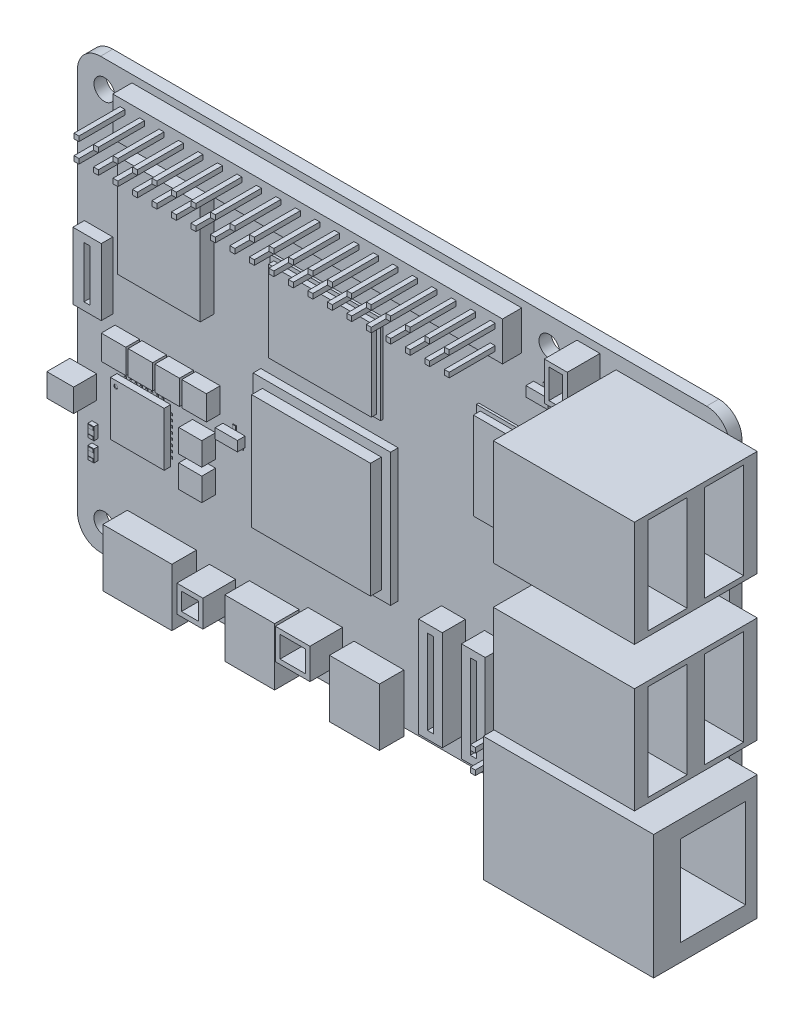
SolidWorks part; units mm, degrees
ref_plane "Front Plane" through (0, 0, 0) normal (0, 0, 1) x (1, 0, 0)
ref_plane "Top Plane" through (0, 0, 0) normal (0, 1, 0) x (1, 0, 0)
ref_plane "Right Plane" through (0, 0, 0) normal (1, 0, 0) x (0, 0, -1)
sketch "Sketch1" plane through (0, 0, 0) normal (0, 0, 1) x (1, 0, 0)
  line L0 (3, 0) -> (82, 0)
  line L1 (85, 3) -> (85, 53)
  line L2 (82, 56) -> (3, 56)
  line L3 (0, 53) -> (0, 3)
  arc A0 (82, 0) -> (85, 3) centre (82, 3) ccw
  arc A1 (85, 53) -> (82, 56) centre (82, 53) ccw
  arc A2 (3, 56) -> (0, 53) centre (3, 53) ccw
  arc A3 (0, 3) -> (3, 0) centre (3, 3) ccw
extrude "PCB" add sketch "Sketch1" along normal blind 1.6
ref_plane "Plane_z1_6" through (0, 0, 1.6) normal (0, 0, 1) x (1, 0, 0)
sketch "Sketch2" plane through (0, 0, 1.6) normal (0, 0, 1) x (1, 0, 0)
  line L1 (7.1, 49.96) -> (57.9, 49.96)
  line L2 (7.1, 49.96) -> (7.1, 55.04)
  line L3 (7.1, 55.04) -> (57.9, 55.04)
  line L4 (57.9, 49.96) -> (57.9, 55.04)
  line L6 (58.76, 6.76) -> (63.84, 6.76)
  line L7 (58.76, 6.76) -> (58.76, 11.84)
  line L8 (58.76, 11.84) -> (63.84, 11.84)
  line L9 (63.84, 6.76) -> (63.84, 11.84)
extrude "Header_Blocks" add sketch "Sketch2" along normal blind 2.5
ref_plane "Plane_z4_1" through (0, 0, 4.1) normal (0, 0, 1) x (1, 0, 0)
sketch "Sketch3" plane through (0, 0, 4.1) normal (0, 0, 1) x (1, 0, 0)
  line L1 (8.05, 50.91) -> (8.69, 50.91)
  line L2 (8.05, 50.91) -> (8.05, 51.55)
  line L3 (8.05, 51.55) -> (8.69, 51.55)
  line L4 (8.69, 50.91) -> (8.69, 51.55)
  line L6 (8.05, 53.45) -> (8.69, 53.45)
  line L7 (8.05, 53.45) -> (8.05, 54.09)
  line L8 (8.05, 54.09) -> (8.69, 54.09)
  line L9 (8.69, 53.45) -> (8.69, 54.09)
  line L11 (10.59, 50.91) -> (11.23, 50.91)
  line L12 (10.59, 50.91) -> (10.59, 51.55)
  line L13 (10.59, 51.55) -> (11.23, 51.55)
  line L14 (11.23, 50.91) -> (11.23, 51.55)
  line L16 (10.59, 53.45) -> (11.23, 53.45)
  line L17 (10.59, 53.45) -> (10.59, 54.09)
  line L18 (10.59, 54.09) -> (11.23, 54.09)
  line L19 (11.23, 53.45) -> (11.23, 54.09)
  line L21 (13.13, 50.91) -> (13.77, 50.91)
  line L22 (13.13, 50.91) -> (13.13, 51.55)
  line L23 (13.13, 51.55) -> (13.77, 51.55)
  line L24 (13.77, 50.91) -> (13.77, 51.55)
  line L26 (13.13, 53.45) -> (13.77, 53.45)
  line L27 (13.13, 53.45) -> (13.13, 54.09)
  line L28 (13.13, 54.09) -> (13.77, 54.09)
  line L29 (13.77, 53.45) -> (13.77, 54.09)
  line L31 (15.67, 50.91) -> (16.31, 50.91)
  line L32 (15.67, 50.91) -> (15.67, 51.55)
  line L33 (15.67, 51.55) -> (16.31, 51.55)
  line L34 (16.31, 50.91) -> (16.31, 51.55)
  line L36 (15.67, 53.45) -> (16.31, 53.45)
  line L37 (15.67, 53.45) -> (15.67, 54.09)
  line L38 (15.67, 54.09) -> (16.31, 54.09)
  line L39 (16.31, 53.45) -> (16.31, 54.09)
  line L41 (18.21, 50.91) -> (18.85, 50.91)
  line L42 (18.21, 50.91) -> (18.21, 51.55)
  line L43 (18.21, 51.55) -> (18.85, 51.55)
  line L44 (18.85, 50.91) -> (18.85, 51.55)
  line L46 (18.21, 53.45) -> (18.85, 53.45)
  line L47 (18.21, 53.45) -> (18.21, 54.09)
  line L48 (18.21, 54.09) -> (18.85, 54.09)
  line L49 (18.85, 53.45) -> (18.85, 54.09)
  line L51 (20.75, 50.91) -> (21.39, 50.91)
  line L52 (20.75, 50.91) -> (20.75, 51.55)
  line L53 (20.75, 51.55) -> (21.39, 51.55)
  line L54 (21.39, 50.91) -> (21.39, 51.55)
  line L56 (20.75, 53.45) -> (21.39, 53.45)
  line L57 (20.75, 53.45) -> (20.75, 54.09)
  line L58 (20.75, 54.09) -> (21.39, 54.09)
  line L59 (21.39, 53.45) -> (21.39, 54.09)
  line L61 (23.29, 50.91) -> (23.93, 50.91)
  line L62 (23.29, 50.91) -> (23.29, 51.55)
  line L63 (23.29, 51.55) -> (23.93, 51.55)
  line L64 (23.93, 50.91) -> (23.93, 51.55)
  line L66 (23.29, 53.45) -> (23.93, 53.45)
  line L67 (23.29, 53.45) -> (23.29, 54.09)
  line L68 (23.29, 54.09) -> (23.93, 54.09)
  line L69 (23.93, 53.45) -> (23.93, 54.09)
  line L71 (25.83, 50.91) -> (26.47, 50.91)
  line L72 (25.83, 50.91) -> (25.83, 51.55)
  line L73 (25.83, 51.55) -> (26.47, 51.55)
  line L74 (26.47, 50.91) -> (26.47, 51.55)
  line L76 (25.83, 53.45) -> (26.47, 53.45)
  line L77 (25.83, 53.45) -> (25.83, 54.09)
  line L78 (25.83, 54.09) -> (26.47, 54.09)
  line L79 (26.47, 53.45) -> (26.47, 54.09)
  line L81 (28.37, 50.91) -> (29.01, 50.91)
  line L82 (28.37, 50.91) -> (28.37, 51.55)
  line L83 (28.37, 51.55) -> (29.01, 51.55)
  line L84 (29.01, 50.91) -> (29.01, 51.55)
  line L86 (28.37, 53.45) -> (29.01, 53.45)
  line L87 (28.37, 53.45) -> (28.37, 54.09)
  line L88 (28.37, 54.09) -> (29.01, 54.09)
  line L89 (29.01, 53.45) -> (29.01, 54.09)
  line L91 (30.91, 50.91) -> (31.55, 50.91)
  line L92 (30.91, 50.91) -> (30.91, 51.55)
  line L93 (30.91, 51.55) -> (31.55, 51.55)
  line L94 (31.55, 50.91) -> (31.55, 51.55)
  line L96 (30.91, 53.45) -> (31.55, 53.45)
  line L97 (30.91, 53.45) -> (30.91, 54.09)
  line L98 (30.91, 54.09) -> (31.55, 54.09)
  line L99 (31.55, 53.45) -> (31.55, 54.09)
  line L101 (33.45, 50.91) -> (34.09, 50.91)
  line L102 (33.45, 50.91) -> (33.45, 51.55)
  line L103 (33.45, 51.55) -> (34.09, 51.55)
  line L104 (34.09, 50.91) -> (34.09, 51.55)
  line L106 (33.45, 53.45) -> (34.09, 53.45)
  line L107 (33.45, 53.45) -> (33.45, 54.09)
  line L108 (33.45, 54.09) -> (34.09, 54.09)
  line L109 (34.09, 53.45) -> (34.09, 54.09)
  line L111 (35.99, 50.91) -> (36.63, 50.91)
  line L112 (35.99, 50.91) -> (35.99, 51.55)
  line L113 (35.99, 51.55) -> (36.63, 51.55)
  line L114 (36.63, 50.91) -> (36.63, 51.55)
  line L116 (35.99, 53.45) -> (36.63, 53.45)
  line L117 (35.99, 53.45) -> (35.99, 54.09)
  line L118 (35.99, 54.09) -> (36.63, 54.09)
  line L119 (36.63, 53.45) -> (36.63, 54.09)
  line L121 (38.53, 50.91) -> (39.17, 50.91)
  line L122 (38.53, 50.91) -> (38.53, 51.55)
  line L123 (38.53, 51.55) -> (39.17, 51.55)
  line L124 (39.17, 50.91) -> (39.17, 51.55)
  line L126 (38.53, 53.45) -> (39.17, 53.45)
  line L127 (38.53, 53.45) -> (38.53, 54.09)
  line L128 (38.53, 54.09) -> (39.17, 54.09)
  line L129 (39.17, 53.45) -> (39.17, 54.09)
  line L131 (41.07, 50.91) -> (41.71, 50.91)
  line L132 (41.07, 50.91) -> (41.07, 51.55)
  line L133 (41.07, 51.55) -> (41.71, 51.55)
  line L134 (41.71, 50.91) -> (41.71, 51.55)
  line L136 (41.07, 53.45) -> (41.71, 53.45)
  line L137 (41.07, 53.45) -> (41.07, 54.09)
  line L138 (41.07, 54.09) -> (41.71, 54.09)
  line L139 (41.71, 53.45) -> (41.71, 54.09)
  line L141 (43.61, 50.91) -> (44.25, 50.91)
  line L142 (43.61, 50.91) -> (43.61, 51.55)
  line L143 (43.61, 51.55) -> (44.25, 51.55)
  line L144 (44.25, 50.91) -> (44.25, 51.55)
  line L146 (43.61, 53.45) -> (44.25, 53.45)
  line L147 (43.61, 53.45) -> (43.61, 54.09)
  line L148 (43.61, 54.09) -> (44.25, 54.09)
  line L149 (44.25, 53.45) -> (44.25, 54.09)
  line L151 (46.15, 50.91) -> (46.79, 50.91)
  line L152 (46.15, 50.91) -> (46.15, 51.55)
  line L153 (46.15, 51.55) -> (46.79, 51.55)
  line L154 (46.79, 50.91) -> (46.79, 51.55)
  line L156 (46.15, 53.45) -> (46.79, 53.45)
  line L157 (46.15, 53.45) -> (46.15, 54.09)
  line L158 (46.15, 54.09) -> (46.79, 54.09)
  line L159 (46.79, 53.45) -> (46.79, 54.09)
  line L161 (48.69, 50.91) -> (49.33, 50.91)
  line L162 (48.69, 50.91) -> (48.69, 51.55)
  line L163 (48.69, 51.55) -> (49.33, 51.55)
  line L164 (49.33, 50.91) -> (49.33, 51.55)
  line L166 (48.69, 53.45) -> (49.33, 53.45)
  line L167 (48.69, 53.45) -> (48.69, 54.09)
  line L168 (48.69, 54.09) -> (49.33, 54.09)
  line L169 (49.33, 53.45) -> (49.33, 54.09)
  line L171 (51.23, 50.91) -> (51.87, 50.91)
  line L172 (51.23, 50.91) -> (51.23, 51.55)
  line L173 (51.23, 51.55) -> (51.87, 51.55)
  line L174 (51.87, 50.91) -> (51.87, 51.55)
  line L176 (51.23, 53.45) -> (51.87, 53.45)
  line L177 (51.23, 53.45) -> (51.23, 54.09)
  line L178 (51.23, 54.09) -> (51.87, 54.09)
  line L179 (51.87, 53.45) -> (51.87, 54.09)
  line L181 (53.77, 50.91) -> (54.41, 50.91)
  line L182 (53.77, 50.91) -> (53.77, 51.55)
  line L183 (53.77, 51.55) -> (54.41, 51.55)
  line L184 (54.41, 50.91) -> (54.41, 51.55)
  line L186 (53.77, 53.45) -> (54.41, 53.45)
  line L187 (53.77, 53.45) -> (53.77, 54.09)
  line L188 (53.77, 54.09) -> (54.41, 54.09)
  line L189 (54.41, 53.45) -> (54.41, 54.09)
  line L191 (56.31, 50.91) -> (56.95, 50.91)
  line L192 (56.31, 50.91) -> (56.31, 51.55)
  line L193 (56.31, 51.55) -> (56.95, 51.55)
  line L194 (56.95, 50.91) -> (56.95, 51.55)
  line L196 (56.31, 53.45) -> (56.95, 53.45)
  line L197 (56.31, 53.45) -> (56.31, 54.09)
  line L198 (56.31, 54.09) -> (56.95, 54.09)
  line L199 (56.95, 53.45) -> (56.95, 54.09)
  line L201 (59.71, 7.71) -> (60.35, 7.71)
  line L202 (59.71, 7.71) -> (59.71, 8.35)
  line L203 (59.71, 8.35) -> (60.35, 8.35)
  line L204 (60.35, 7.71) -> (60.35, 8.35)
  line L206 (59.71, 10.25) -> (60.35, 10.25)
  line L207 (59.71, 10.25) -> (59.71, 10.89)
  line L208 (59.71, 10.89) -> (60.35, 10.89)
  line L209 (60.35, 10.25) -> (60.35, 10.89)
  line L211 (62.25, 7.71) -> (62.89, 7.71)
  line L212 (62.25, 7.71) -> (62.25, 8.35)
  line L213 (62.25, 8.35) -> (62.89, 8.35)
  line L214 (62.89, 7.71) -> (62.89, 8.35)
  line L216 (62.25, 10.25) -> (62.89, 10.25)
  line L217 (62.25, 10.25) -> (62.25, 10.89)
  line L218 (62.25, 10.89) -> (62.89, 10.89)
  line L219 (62.89, 10.25) -> (62.89, 10.89)
extrude "Header_Pins" add sketch "Sketch3" along normal blind 6
sketch "Sketch4" plane through (0, 0, 1.6) normal (0, 0, 1) x (1, 0, 0)
  line L1 (6.125, 14.1) -> (6.375, 14.1)
  line L2 (6.125, 14.1) -> (6.125, 14.4)
  line L3 (6.125, 14.4) -> (6.375, 14.4)
  line L4 (6.375, 14.1) -> (6.375, 14.4)
  line L6 (5, 15.225) -> (5.3, 15.225)
  line L7 (5, 15.225) -> (5, 15.475)
  line L8 (5, 15.475) -> (5.3, 15.475)
  line L9 (5.3, 15.225) -> (5.3, 15.475)
  line L11 (6.125, 21.2) -> (6.375, 21.2)
  line L12 (6.125, 21.2) -> (6.125, 21.5)
  line L13 (6.125, 21.5) -> (6.375, 21.5)
  line L14 (6.375, 21.2) -> (6.375, 21.5)
  line L16 (12.1, 15.225) -> (12.4, 15.225)
  line L17 (12.1, 15.225) -> (12.1, 15.475)
  line L18 (12.1, 15.475) -> (12.4, 15.475)
  line L19 (12.4, 15.225) -> (12.4, 15.475)
  line L21 (6.825, 14.1) -> (7.075, 14.1)
  line L22 (6.825, 14.1) -> (6.825, 14.4)
  line L23 (6.825, 14.4) -> (7.075, 14.4)
  line L24 (7.075, 14.1) -> (7.075, 14.4)
  line L26 (5, 15.925) -> (5.3, 15.925)
  line L27 (5, 15.925) -> (5, 16.175)
  line L28 (5, 16.175) -> (5.3, 16.175)
  line L29 (5.3, 15.925) -> (5.3, 16.175)
  line L31 (6.825, 21.2) -> (7.075, 21.2)
  line L32 (6.825, 21.2) -> (6.825, 21.5)
  line L33 (6.825, 21.5) -> (7.075, 21.5)
  line L34 (7.075, 21.2) -> (7.075, 21.5)
  line L36 (12.1, 15.925) -> (12.4, 15.925)
  line L37 (12.1, 15.925) -> (12.1, 16.175)
  line L38 (12.1, 16.175) -> (12.4, 16.175)
  line L39 (12.4, 15.925) -> (12.4, 16.175)
  line L41 (7.525, 14.1) -> (7.775, 14.1)
  line L42 (7.525, 14.1) -> (7.525, 14.4)
  line L43 (7.525, 14.4) -> (7.775, 14.4)
  line L44 (7.775, 14.1) -> (7.775, 14.4)
  line L46 (5, 16.625) -> (5.3, 16.625)
  line L47 (5, 16.625) -> (5, 16.875)
  line L48 (5, 16.875) -> (5.3, 16.875)
  line L49 (5.3, 16.625) -> (5.3, 16.875)
  line L51 (7.525, 21.2) -> (7.775, 21.2)
  line L52 (7.525, 21.2) -> (7.525, 21.5)
  line L53 (7.525, 21.5) -> (7.775, 21.5)
  line L54 (7.775, 21.2) -> (7.775, 21.5)
  line L56 (12.1, 16.625) -> (12.4, 16.625)
  line L57 (12.1, 16.625) -> (12.1, 16.875)
  line L58 (12.1, 16.875) -> (12.4, 16.875)
  line L59 (12.4, 16.625) -> (12.4, 16.875)
  line L61 (8.225, 14.1) -> (8.475, 14.1)
  line L62 (8.225, 14.1) -> (8.225, 14.4)
  line L63 (8.225, 14.4) -> (8.475, 14.4)
  line L64 (8.475, 14.1) -> (8.475, 14.4)
  line L66 (5, 17.325) -> (5.3, 17.325)
  line L67 (5, 17.325) -> (5, 17.575)
  line L68 (5, 17.575) -> (5.3, 17.575)
  line L69 (5.3, 17.325) -> (5.3, 17.575)
  line L71 (8.225, 21.2) -> (8.475, 21.2)
  line L72 (8.225, 21.2) -> (8.225, 21.5)
  line L73 (8.225, 21.5) -> (8.475, 21.5)
  line L74 (8.475, 21.2) -> (8.475, 21.5)
  line L76 (12.1, 17.325) -> (12.4, 17.325)
  line L77 (12.1, 17.325) -> (12.1, 17.575)
  line L78 (12.1, 17.575) -> (12.4, 17.575)
  line L79 (12.4, 17.325) -> (12.4, 17.575)
  line L81 (8.925, 14.1) -> (9.175, 14.1)
  line L82 (8.925, 14.1) -> (8.925, 14.4)
  line L83 (8.925, 14.4) -> (9.175, 14.4)
  line L84 (9.175, 14.1) -> (9.175, 14.4)
  line L86 (5, 18.025) -> (5.3, 18.025)
  line L87 (5, 18.025) -> (5, 18.275)
  line L88 (5, 18.275) -> (5.3, 18.275)
  line L89 (5.3, 18.025) -> (5.3, 18.275)
  line L91 (8.925, 21.2) -> (9.175, 21.2)
  line L92 (8.925, 21.2) -> (8.925, 21.5)
  line L93 (8.925, 21.5) -> (9.175, 21.5)
  line L94 (9.175, 21.2) -> (9.175, 21.5)
  line L96 (12.1, 18.025) -> (12.4, 18.025)
  line L97 (12.1, 18.025) -> (12.1, 18.275)
  line L98 (12.1, 18.275) -> (12.4, 18.275)
  line L99 (12.4, 18.025) -> (12.4, 18.275)
  line L101 (9.625, 14.1) -> (9.875, 14.1)
  line L102 (9.625, 14.1) -> (9.625, 14.4)
  line L103 (9.625, 14.4) -> (9.875, 14.4)
  line L104 (9.875, 14.1) -> (9.875, 14.4)
  line L106 (5, 18.725) -> (5.3, 18.725)
  line L107 (5, 18.725) -> (5, 18.975)
  line L108 (5, 18.975) -> (5.3, 18.975)
  line L109 (5.3, 18.725) -> (5.3, 18.975)
  line L111 (9.625, 21.2) -> (9.875, 21.2)
  line L112 (9.625, 21.2) -> (9.625, 21.5)
  line L113 (9.625, 21.5) -> (9.875, 21.5)
  line L114 (9.875, 21.2) -> (9.875, 21.5)
  line L116 (12.1, 18.725) -> (12.4, 18.725)
  line L117 (12.1, 18.725) -> (12.1, 18.975)
  line L118 (12.1, 18.975) -> (12.4, 18.975)
  line L119 (12.4, 18.725) -> (12.4, 18.975)
  line L121 (10.325, 14.1) -> (10.575, 14.1)
  line L122 (10.325, 14.1) -> (10.325, 14.4)
  line L123 (10.325, 14.4) -> (10.575, 14.4)
  line L124 (10.575, 14.1) -> (10.575, 14.4)
  line L126 (5, 19.425) -> (5.3, 19.425)
  line L127 (5, 19.425) -> (5, 19.675)
  line L128 (5, 19.675) -> (5.3, 19.675)
  line L129 (5.3, 19.425) -> (5.3, 19.675)
  line L131 (10.325, 21.2) -> (10.575, 21.2)
  line L132 (10.325, 21.2) -> (10.325, 21.5)
  line L133 (10.325, 21.5) -> (10.575, 21.5)
  line L134 (10.575, 21.2) -> (10.575, 21.5)
  line L136 (12.1, 19.425) -> (12.4, 19.425)
  line L137 (12.1, 19.425) -> (12.1, 19.675)
  line L138 (12.1, 19.675) -> (12.4, 19.675)
  line L139 (12.4, 19.425) -> (12.4, 19.675)
  line L141 (11.025, 14.1) -> (11.275, 14.1)
  line L142 (11.025, 14.1) -> (11.025, 14.4)
  line L143 (11.025, 14.4) -> (11.275, 14.4)
  line L144 (11.275, 14.1) -> (11.275, 14.4)
  line L146 (5, 20.125) -> (5.3, 20.125)
  line L147 (5, 20.125) -> (5, 20.375)
  line L148 (5, 20.375) -> (5.3, 20.375)
  line L149 (5.3, 20.125) -> (5.3, 20.375)
  line L151 (11.025, 21.2) -> (11.275, 21.2)
  line L152 (11.025, 21.2) -> (11.025, 21.5)
  line L153 (11.025, 21.5) -> (11.275, 21.5)
  line L154 (11.275, 21.2) -> (11.275, 21.5)
  line L156 (12.1, 20.125) -> (12.4, 20.125)
  line L157 (12.1, 20.125) -> (12.1, 20.375)
  line L158 (12.1, 20.375) -> (12.4, 20.375)
  line L159 (12.4, 20.125) -> (12.4, 20.375)
  line L161 (66.275, 43.15) -> (66.525, 43.15)
  line L162 (66.275, 43.15) -> (66.275, 43.45)
  line L163 (66.275, 43.45) -> (66.525, 43.45)
  line L164 (66.525, 43.15) -> (66.525, 43.45)
  line L166 (65.2, 44.475) -> (65.5, 44.475)
  line L167 (65.2, 44.475) -> (65.2, 44.725)
  line L168 (65.2, 44.725) -> (65.5, 44.725)
  line L169 (65.5, 44.475) -> (65.5, 44.725)
  line L171 (66.275, 47.75) -> (66.525, 47.75)
  line L172 (66.275, 47.75) -> (66.275, 48.05)
  line L173 (66.275, 48.05) -> (66.525, 48.05)
  line L174 (66.525, 47.75) -> (66.525, 48.05)
  line L176 (69.3, 44.475) -> (69.6, 44.475)
  line L177 (69.3, 44.475) -> (69.3, 44.725)
  line L178 (69.3, 44.725) -> (69.6, 44.725)
  line L179 (69.6, 44.475) -> (69.6, 44.725)
  line L181 (66.9417, 43.15) -> (67.1917, 43.15)
  line L182 (66.9417, 43.15) -> (66.9417, 43.45)
  line L183 (66.9417, 43.45) -> (67.1917, 43.45)
  line L184 (67.1917, 43.15) -> (67.1917, 43.45)
  line L186 (65.2, 45.1417) -> (65.5, 45.1417)
  line L187 (65.2, 45.1417) -> (65.2, 45.3917)
  line L188 (65.2, 45.3917) -> (65.5, 45.3917)
  line L189 (65.5, 45.1417) -> (65.5, 45.3917)
  line L191 (66.9417, 47.75) -> (67.1917, 47.75)
  line L192 (66.9417, 47.75) -> (66.9417, 48.05)
  line L193 (66.9417, 48.05) -> (67.1917, 48.05)
  line L194 (67.1917, 47.75) -> (67.1917, 48.05)
  line L196 (69.3, 45.1417) -> (69.6, 45.1417)
  line L197 (69.3, 45.1417) -> (69.3, 45.3917)
  line L198 (69.3, 45.3917) -> (69.6, 45.3917)
  line L199 (69.6, 45.1417) -> (69.6, 45.3917)
  line L201 (67.6083, 43.15) -> (67.8583, 43.15)
  line L202 (67.6083, 43.15) -> (67.6083, 43.45)
  line L203 (67.6083, 43.45) -> (67.8583, 43.45)
  line L204 (67.8583, 43.15) -> (67.8583, 43.45)
  line L206 (65.2, 45.8083) -> (65.5, 45.8083)
  line L207 (65.2, 45.8083) -> (65.2, 46.0583)
  line L208 (65.2, 46.0583) -> (65.5, 46.0583)
  line L209 (65.5, 45.8083) -> (65.5, 46.0583)
  line L211 (67.6083, 47.75) -> (67.8583, 47.75)
  line L212 (67.6083, 47.75) -> (67.6083, 48.05)
  line L213 (67.6083, 48.05) -> (67.8583, 48.05)
  line L214 (67.8583, 47.75) -> (67.8583, 48.05)
  line L216 (69.3, 45.8083) -> (69.6, 45.8083)
  line L217 (69.3, 45.8083) -> (69.3, 46.0583)
  line L218 (69.3, 46.0583) -> (69.6, 46.0583)
  line L219 (69.6, 45.8083) -> (69.6, 46.0583)
  line L221 (68.275, 43.15) -> (68.525, 43.15)
  line L222 (68.275, 43.15) -> (68.275, 43.45)
  line L223 (68.275, 43.45) -> (68.525, 43.45)
  line L224 (68.525, 43.15) -> (68.525, 43.45)
  line L226 (65.2, 46.475) -> (65.5, 46.475)
  line L227 (65.2, 46.475) -> (65.2, 46.725)
  line L228 (65.2, 46.725) -> (65.5, 46.725)
  line L229 (65.5, 46.475) -> (65.5, 46.725)
  line L231 (68.275, 47.75) -> (68.525, 47.75)
  line L232 (68.275, 47.75) -> (68.275, 48.05)
  line L233 (68.275, 48.05) -> (68.525, 48.05)
  line L234 (68.525, 47.75) -> (68.525, 48.05)
  line L236 (69.3, 46.475) -> (69.6, 46.475)
  line L237 (69.3, 46.475) -> (69.3, 46.725)
  line L238 (69.3, 46.725) -> (69.6, 46.725)
  line L239 (69.6, 46.475) -> (69.6, 46.725)
extrude "Parts_add00" add sketch "Sketch4" along normal blind 0.05
sketch "Sketch5" plane through (0, 0, 1.6) normal (0, 0, 1) x (1, 0, 0)
  line L1 (19.35, 20.85) -> (19.75, 20.85)
  line L2 (19.35, 20.85) -> (19.35, 21.55)
  line L3 (19.35, 21.55) -> (19.75, 21.55)
  line L4 (19.75, 20.85) -> (19.75, 21.55)
  line L6 (21.25, 20.85) -> (21.65, 20.85)
  line L7 (21.25, 20.85) -> (21.25, 21.55)
  line L8 (21.25, 21.55) -> (21.65, 21.55)
  line L9 (21.65, 20.85) -> (21.65, 21.55)
  line L11 (20.3, 22.45) -> (20.7, 22.45)
  line L12 (20.3, 22.45) -> (20.3, 23.15)
  line L13 (20.3, 23.15) -> (20.7, 23.15)
  line L14 (20.7, 22.45) -> (20.7, 23.15)
  line L16 (58.35, 16.85) -> (58.75, 16.85)
  line L17 (58.35, 16.85) -> (58.35, 17.55)
  line L18 (58.35, 17.55) -> (58.75, 17.55)
  line L19 (58.75, 16.85) -> (58.75, 17.55)
  line L21 (60.25, 16.85) -> (60.65, 16.85)
  line L22 (60.25, 16.85) -> (60.25, 17.55)
  line L23 (60.25, 17.55) -> (60.65, 17.55)
  line L24 (60.65, 16.85) -> (60.65, 17.55)
  line L26 (59.3, 18.45) -> (59.7, 18.45)
  line L27 (59.3, 18.45) -> (59.3, 19.15)
  line L28 (59.3, 19.15) -> (59.7, 19.15)
  line L29 (59.7, 18.45) -> (59.7, 19.15)
  line L31 (59.85, 45.85) -> (60.25, 45.85)
  line L32 (59.85, 45.85) -> (59.85, 46.55)
  line L33 (59.85, 46.55) -> (60.25, 46.55)
  line L34 (60.25, 45.85) -> (60.25, 46.55)
  line L36 (61.75, 45.85) -> (62.15, 45.85)
  line L37 (61.75, 45.85) -> (61.75, 46.55)
  line L38 (61.75, 46.55) -> (62.15, 46.55)
  line L39 (62.15, 45.85) -> (62.15, 46.55)
  line L41 (60.8, 47.45) -> (61.2, 47.45)
  line L42 (60.8, 47.45) -> (60.8, 48.15)
  line L43 (60.8, 48.15) -> (61.2, 48.15)
  line L44 (61.2, 47.45) -> (61.2, 48.15)
extrude "Parts_add01" add sketch "Sketch5" along normal blind 0.1
sketch "Sketch6" plane through (0, 0, 1.6) normal (0, 0, 1) x (1, 0, 0)
  line L1 (25.4, 33.4) -> (39.8, 33.4)
  line L2 (25.4, 33.4) -> (25.4, 45)
  line L3 (25.4, 45) -> (39.8, 45)
  line L4 (39.8, 33.4) -> (39.8, 45)
  line L6 (52.3, 29.1) -> (65.2, 29.1)
  line L7 (52.3, 29.1) -> (52.3, 41.5)
  line L8 (52.3, 41.5) -> (65.2, 41.5)
  line L9 (65.2, 29.1) -> (65.2, 41.5)
extrude "Parts_add02" add sketch "Sketch6" along normal blind 0.3
sketch "Sketch7" plane through (0, 0, 1.6) normal (0, 0, 1) x (1, 0, 0)
  line L1 (1.9, 10.2) -> (2.7, 10.2)
  line L2 (1.9, 10.2) -> (1.9, 11.8)
  line L3 (1.9, 11.8) -> (2.7, 11.8)
  line L4 (2.7, 10.2) -> (2.7, 11.8)
  line L6 (1.9, 12.7) -> (2.7, 12.7)
  line L7 (1.9, 12.7) -> (1.9, 14.3)
  line L8 (1.9, 14.3) -> (2.7, 14.3)
  line L9 (2.7, 12.7) -> (2.7, 14.3)
extrude "Parts_add03" add sketch "Sketch7" along normal blind 0.55
sketch "Sketch8" plane through (0, 0, 1.6) normal (0, 0, 1) x (1, 0, 0)
  line L0 (62.7, 19.918) -> (65.882, 23.1)
  line L1 (65.882, 23.1) -> (62.7, 26.282)
  line L2 (62.7, 26.282) -> (59.518, 23.1)
  line L3 (59.518, 23.1) -> (62.7, 19.918)
extrude "Parts_add04" add sketch "Sketch8" along normal blind 0.9
sketch "Sketch9" plane through (0, 0, 1.6) normal (0, 0, 1) x (1, 0, 0)
  line L1 (23.9, 13.9) -> (41.8, 13.9)
  line L2 (23.9, 13.9) -> (23.9, 31.2)
  line L3 (23.9, 31.2) -> (41.8, 31.2)
  line L4 (41.8, 13.9) -> (41.8, 31.2)
extrude "Parts_add05" add sketch "Sketch9" along normal blind 1
sketch "Sketch10" plane through (0, 0, 1.6) normal (0, 0, 1) x (1, 0, 0)
  line L1 (0.9, 27.7) -> (4.6, 27.7)
  line L2 (0.9, 27.7) -> (0.9, 36.4)
  line L3 (0.9, 36.4) -> (4.6, 36.4)
  line L4 (4.6, 27.7) -> (4.6, 36.4)
extrude "Parts_add06" add sketch "Sketch10" along normal blind 1.5
sketch "Sketch11" plane through (0, 0, 1.6) normal (0, 0, 1) x (1, 0, 0)
  line L1 (7, 34.3) -> (17.8, 34.3)
  line L2 (7, 34.3) -> (7, 47.6)
  line L3 (7, 47.6) -> (17.8, 47.6)
  line L4 (17.8, 34.3) -> (17.8, 47.6)
  line L6 (4.9, 23.4) -> (8.1, 23.4)
  line L7 (4.9, 23.4) -> (4.9, 26.6)
  line L8 (4.9, 26.6) -> (8.1, 26.6)
  line L9 (8.1, 23.4) -> (8.1, 26.6)
  line L11 (8.4, 23.4) -> (11.6, 23.4)
  line L12 (8.4, 23.4) -> (8.4, 26.6)
  line L13 (8.4, 26.6) -> (11.6, 26.6)
  line L14 (11.6, 23.4) -> (11.6, 26.6)
  line L16 (11.9, 23.4) -> (15.1, 23.4)
  line L17 (11.9, 23.4) -> (11.9, 26.6)
  line L18 (11.9, 26.6) -> (15.1, 26.6)
  line L19 (15.1, 23.4) -> (15.1, 26.6)
  line L21 (15.4, 23.4) -> (18.6, 23.4)
  line L22 (15.4, 23.4) -> (15.4, 26.6)
  line L23 (15.4, 26.6) -> (18.6, 26.6)
  line L24 (18.6, 23.4) -> (18.6, 26.6)
  line L26 (15, 18) -> (18, 18)
  line L27 (15, 18) -> (15, 21)
  line L28 (15, 21) -> (18, 21)
  line L29 (18, 18) -> (18, 21)
  line L31 (15, 14) -> (18, 14)
  line L32 (15, 14) -> (15, 17)
  line L33 (15, 17) -> (18, 17)
  line L34 (18, 14) -> (18, 17)
extrude "Parts_add07" add sketch "Sketch11" along normal blind 1.8
sketch "Sketch12" plane through (0, 0, 1.6) normal (0, 0, 1) x (1, 0, 0)
  line L1 (53.05, 3.2) -> (56.15, 3.2)
  line L2 (53.05, 3.2) -> (53.05, 16.2)
  line L3 (53.05, 16.2) -> (56.15, 16.2)
  line L4 (56.15, 3.2) -> (56.15, 16.2)
  line L6 (47.45, 3.2) -> (50.55, 3.2)
  line L7 (47.45, 3.2) -> (47.45, 16.2)
  line L8 (47.45, 16.2) -> (50.55, 16.2)
  line L9 (50.55, 3.2) -> (50.55, 16.2)
  line L11 (-1, 16.9) -> (2.5, 16.9)
  line L12 (-1, 16.9) -> (-1, 19.9)
  line L13 (-1, 19.9) -> (2.5, 19.9)
  line L14 (2.5, 16.9) -> (2.5, 19.9)
extrude "Parts_add08" add sketch "Sketch12" along normal blind 3
sketch "Sketch13" plane through (0, 0, 1.6) normal (0, 0, 1) x (1, 0, 0)
  line L1 (22.4, -1) -> (28.9, -1)
  line L2 (22.4, -1) -> (22.4, 6.5)
  line L3 (22.4, 6.5) -> (28.9, 6.5)
  line L4 (28.9, -1) -> (28.9, 6.5)
  line L6 (36.05, -1) -> (42.55, -1)
  line L7 (36.05, -1) -> (36.05, 6.5)
  line L8 (36.05, 6.5) -> (42.55, 6.5)
  line L9 (42.55, -1) -> (42.55, 6.5)
  line L11 (6.5, -1) -> (15.5, -1)
  line L12 (6.5, -1) -> (6.5, 6.5)
  line L13 (6.5, 6.5) -> (15.5, 6.5)
  line L14 (15.5, -1) -> (15.5, 6.5)
extrude "Parts_add09" add sketch "Sketch13" along normal blind 3.2
sketch "Sketch14" plane through (0, 0, 1.6) normal (0, 0, 1) x (1, 0, 0)
  line L1 (65.1, 50) -> (68.1, 50)
  line L2 (65.1, 50) -> (65.1, 55)
  line L3 (65.1, 55) -> (68.1, 55)
  line L4 (68.1, 50) -> (68.1, 55)
  line L6 (30.05, 3.3) -> (34.55, 3.3)
  line L7 (30.05, 3.3) -> (30.05, 7.3)
  line L8 (30.05, 7.3) -> (34.55, 7.3)
  line L9 (34.55, 3.3) -> (34.55, 7.3)
  line L11 (17.2, 2.25) -> (20.6, 2.25)
  line L12 (17.2, 2.25) -> (17.2, 5.75)
  line L13 (17.2, 5.75) -> (20.6, 5.75)
  line L14 (20.6, 2.25) -> (20.6, 5.75)
extrude "Parts_add10" add sketch "Sketch14" along normal blind 4.25
sketch "Sketch15" plane through (0, 0, 1.6) normal (0, 0, 1) x (1, 0, 0)
  line L1 (66.4, 1.5) -> (88.6, 1.5)
  line L2 (66.4, 1.5) -> (66.4, 17.7)
  line L3 (66.4, 17.7) -> (88.6, 17.7)
  line L4 (88.6, 1.5) -> (88.6, 17.7)
extrude "Parts_add11" add sketch "Sketch15" along normal blind 13.5
sketch "Sketch16" plane through (0, 0, 1.6) normal (0, 0, 1) x (1, 0, 0)
  line L1 (70.2, 40.4) -> (88.6, 40.4)
  line L2 (70.2, 40.4) -> (70.2, 54.2)
  line L3 (70.2, 54.2) -> (88.6, 54.2)
  line L4 (88.6, 40.4) -> (88.6, 54.2)
  line L6 (70.2, 21.6) -> (88.6, 21.6)
  line L7 (70.2, 21.6) -> (70.2, 35.4)
  line L8 (70.2, 35.4) -> (88.6, 35.4)
  line L9 (88.6, 21.6) -> (88.6, 35.4)
extrude "Parts_add12" add sketch "Sketch16" along normal blind 16
ref_plane "Plane_z1_65" through (0, 0, 1.65) normal (0, 0, 1) x (1, 0, 0)
sketch "Sketch17" plane through (0, 0, 1.65) normal (0, 0, 1) x (1, 0, 0)
  line L1 (5.2, 14.3) -> (12.2, 14.3)
  line L2 (5.2, 14.3) -> (5.2, 21.3)
  line L3 (5.2, 21.3) -> (12.2, 21.3)
  line L4 (12.2, 14.3) -> (12.2, 21.3)
extrude "Parts_add13" add sketch "Sketch17" along normal blind 0.85
sketch "Sketch18" plane through (0, 0, 1.65) normal (0, 0, 1) x (1, 0, 0)
  line L1 (65.4, 43.35) -> (69.4, 43.35)
  line L2 (65.4, 43.35) -> (65.4, 47.85)
  line L3 (65.4, 47.85) -> (69.4, 47.85)
  line L4 (69.4, 43.35) -> (69.4, 47.85)
extrude "Parts_add14" add sketch "Sketch18" along normal blind 0.95
ref_plane "Plane_z1_7" through (0, 0, 1.7) normal (0, 0, 1) x (1, 0, 0)
sketch "Sketch19" plane through (0, 0, 1.7) normal (0, 0, 1) x (1, 0, 0)
  line L1 (19.05, 21.35) -> (21.95, 21.35)
  line L2 (19.05, 21.35) -> (19.05, 22.65)
  line L3 (19.05, 22.65) -> (21.95, 22.65)
  line L4 (21.95, 21.35) -> (21.95, 22.65)
  line L6 (58.05, 17.35) -> (60.95, 17.35)
  line L7 (58.05, 17.35) -> (58.05, 18.65)
  line L8 (58.05, 18.65) -> (60.95, 18.65)
  line L9 (60.95, 17.35) -> (60.95, 18.65)
  line L11 (59.55, 46.35) -> (62.45, 46.35)
  line L12 (59.55, 46.35) -> (59.55, 47.65)
  line L13 (59.55, 47.65) -> (62.45, 47.65)
  line L14 (62.45, 46.35) -> (62.45, 47.65)
extrude "Parts_add15" add sketch "Sketch19" along normal blind 1
ref_plane "Plane_z1_9" through (0, 0, 1.9) normal (0, 0, 1) x (1, 0, 0)
sketch "Sketch20" plane through (0, 0, 1.9) normal (0, 0, 1) x (1, 0, 0)
  line L1 (25.9, 33.9) -> (39.3, 33.9)
  line L2 (25.9, 33.9) -> (25.9, 44.5)
  line L3 (25.9, 44.5) -> (39.3, 44.5)
  line L4 (39.3, 33.9) -> (39.3, 44.5)
extrude "Parts_add16" add sketch "Sketch20" along normal blind 0.7
sketch "Sketch21" plane through (0, 0, 1.9) normal (0, 0, 1) x (1, 0, 0)
  line L1 (52.8, 29.6) -> (64.7, 29.6)
  line L2 (52.8, 29.6) -> (52.8, 41)
  line L3 (52.8, 41) -> (64.7, 41)
  line L4 (64.7, 29.6) -> (64.7, 41)
extrude "Parts_add17" add sketch "Sketch21" along normal blind 0.9
ref_plane "Plane_z2_15" through (0, 0, 2.15) normal (0, 0, 1) x (1, 0, 0)
sketch "Sketch22" plane through (0, 0, 2.15) normal (0, 0, 1) x (1, 0, 0)
  line L1 (1.95, 10.25) -> (2.65, 10.25)
  line L2 (1.95, 10.25) -> (1.95, 10.65)
  line L3 (1.95, 10.65) -> (2.65, 10.65)
  line L4 (2.65, 10.25) -> (2.65, 10.65)
  line L6 (1.95, 11.35) -> (2.65, 11.35)
  line L7 (1.95, 11.35) -> (1.95, 11.75)
  line L8 (1.95, 11.75) -> (2.65, 11.75)
  line L9 (2.65, 11.35) -> (2.65, 11.75)
  line L11 (1.95, 12.75) -> (2.65, 12.75)
  line L12 (1.95, 12.75) -> (1.95, 13.15)
  line L13 (1.95, 13.15) -> (2.65, 13.15)
  line L14 (2.65, 12.75) -> (2.65, 13.15)
  line L16 (1.95, 13.85) -> (2.65, 13.85)
  line L17 (1.95, 13.85) -> (1.95, 14.25)
  line L18 (1.95, 14.25) -> (2.65, 14.25)
  line L19 (2.65, 13.85) -> (2.65, 14.25)
extrude "Parts_add18" add sketch "Sketch22" along normal blind 0.05
ref_plane "Plane_z2_6" through (0, 0, 2.6) normal (0, 0, 1) x (1, 0, 0)
sketch "Sketch23" plane through (0, 0, 2.6) normal (0, 0, 1) x (1, 0, 0)
  line L1 (25.1, 15.05) -> (40.6, 15.05)
  line L2 (25.1, 15.05) -> (25.1, 30.05)
  line L3 (25.1, 30.05) -> (40.6, 30.05)
  line L4 (40.6, 15.05) -> (40.6, 30.05)
extrude "Parts_add19" add sketch "Sketch23" along normal blind 1.4
ref_plane "Plane_x88_6" through (88.6, 0, 0) normal (1, 0, 0) x (0, 0, -1)
sketch "Sketch24" plane through (88.6, 0, 0) normal (1, 0, 0) x (0, 0, -1)
  line L1 (-3.37, 41.05) -> (-8.47, 41.05)
  line L2 (-3.37, 41.05) -> (-3.37, 53.55)
  line L3 (-3.37, 53.55) -> (-8.47, 53.55)
  line L4 (-8.47, 41.05) -> (-8.47, 53.55)
  line L6 (-10.73, 41.05) -> (-15.83, 41.05)
  line L7 (-10.73, 41.05) -> (-10.73, 53.55)
  line L8 (-10.73, 53.55) -> (-15.83, 53.55)
  line L9 (-15.83, 41.05) -> (-15.83, 53.55)
  line L11 (-3.37, 22.25) -> (-8.47, 22.25)
  line L12 (-3.37, 22.25) -> (-3.37, 34.75)
  line L13 (-3.37, 34.75) -> (-8.47, 34.75)
  line L14 (-8.47, 22.25) -> (-8.47, 34.75)
  line L16 (-10.73, 22.25) -> (-15.83, 22.25)
  line L17 (-10.73, 22.25) -> (-10.73, 34.75)
  line L18 (-10.73, 34.75) -> (-15.83, 34.75)
  line L19 (-15.83, 22.25) -> (-15.83, 34.75)
extrude "Parts_cut00" cut sketch "Sketch24" against normal blind 14
sketch "Sketch25" plane through (88.6, 0, 0) normal (1, 0, 0) x (0, 0, -1)
  line L1 (-3.1, 3.75) -> (-11.6, 3.75)
  line L2 (-3.1, 3.75) -> (-3.1, 15.45)
  line L3 (-3.1, 15.45) -> (-11.6, 15.45)
  line L4 (-11.6, 3.75) -> (-11.6, 15.45)
extrude "Parts_cut01" cut sketch "Sketch25" against normal blind 18
ref_plane "Plane_y6" through (0, 6, 0) normal (0, 1, 0) x (1, 0, 0)
sketch "Sketch26" plane through (0, 6, 0) normal (0, 1, 0) x (1, 0, 0)
  line L0 (8.1, -3.2) -> (13.9, -3.2) construction
  line L1 (22.9, -2.2) -> (28.4, -2.2)
  line L2 (22.9, -2.2) -> (22.9, -4.2)
  line L3 (22.9, -4.2) -> (28.4, -4.2)
  line L4 (28.4, -2.2) -> (28.4, -4.2)
  line L5 (8.1, -1.95) -> (13.9, -1.95)
  line L6 (36.55, -2.2) -> (42.05, -2.2)
  line L7 (36.55, -2.2) -> (36.55, -4.2)
  line L8 (36.55, -4.2) -> (42.05, -4.2)
  line L9 (42.05, -2.2) -> (42.05, -4.2)
  line L10 (8.1, -4.45) -> (13.9, -4.45)
  arc A0 (8.1, -1.95) -> (8.1, -4.45) centre (8.1, -3.2) ccw
  arc A1 (13.9, -4.45) -> (13.9, -1.95) centre (13.9, -3.2) ccw
  point P4 (11, -3.2)
extrude "Parts_cut02" cut sketch "Sketch26" against normal blind 7
ref_plane "Plane_z2_5" through (0, 0, 2.5) normal (0, 0, 1) x (1, 0, 0)
sketch "Sketch27" plane through (0, 0, 2.5) normal (0, 0, 1) x (1, 0, 0)
  circle A0 centre (5.9, 20.6) radius 0.25
extrude "Parts_cut03" cut sketch "Sketch27" against normal blind 0.1
sketch "Sketch28" plane through (0, 0, 2.6) normal (0, 0, 1) x (1, 0, 0)
  circle A0 centre (66.1, 47.15) radius 0.25
extrude "Parts_cut04" cut sketch "Sketch28" against normal blind 0.1
ref_plane "Plane_z3_1" through (0, 0, 3.1) normal (0, 0, 1) x (1, 0, 0)
sketch "Sketch29" plane through (0, 0, 3.1) normal (0, 0, 1) x (1, 0, 0)
  line L1 (2.35, 28.7) -> (3.15, 28.7)
  line L2 (2.35, 28.7) -> (2.35, 35.4)
  line L3 (2.35, 35.4) -> (3.15, 35.4)
  line L4 (3.15, 28.7) -> (3.15, 35.4)
extrude "Parts_cut05" cut sketch "Sketch29" against normal blind 1
ref_plane "Plane_z4_6" through (0, 0, 4.6) normal (0, 0, 1) x (1, 0, 0)
sketch "Sketch30" plane through (0, 0, 4.6) normal (0, 0, 1) x (1, 0, 0)
  line L1 (54.2, 4.2) -> (55, 4.2)
  line L2 (54.2, 4.2) -> (54.2, 15.2)
  line L3 (54.2, 15.2) -> (55, 15.2)
  line L4 (55, 4.2) -> (55, 15.2)
  line L6 (48.6, 4.2) -> (49.4, 4.2)
  line L7 (48.6, 4.2) -> (48.6, 15.2)
  line L8 (48.6, 15.2) -> (49.4, 15.2)
  line L9 (49.4, 4.2) -> (49.4, 15.2)
extrude "Parts_cut06" cut sketch "Sketch30" against normal blind 2.5
ref_plane "Plane_z5_85" through (0, 0, 5.85) normal (0, 0, 1) x (1, 0, 0)
sketch "Sketch31" plane through (0, 0, 5.85) normal (0, 0, 1) x (1, 0, 0)
  line L1 (65.7, 50.6) -> (67.5, 50.6)
  line L2 (65.7, 50.6) -> (65.7, 54.4)
  line L3 (65.7, 54.4) -> (67.5, 54.4)
  line L4 (67.5, 50.6) -> (67.5, 54.4)
  line L6 (30.65, 3.9) -> (33.95, 3.9)
  line L7 (30.65, 3.9) -> (30.65, 6.7)
  line L8 (30.65, 6.7) -> (33.95, 6.7)
  line L9 (33.95, 3.9) -> (33.95, 6.7)
  line L11 (17.8, 2.85) -> (20, 2.85)
  line L12 (17.8, 2.85) -> (17.8, 5.15)
  line L13 (17.8, 5.15) -> (20, 5.15)
  line L14 (20, 2.85) -> (20, 5.15)
extrude "Parts_cut07" cut sketch "Sketch31" against normal blind 3.25
sketch "Sketch32" plane through (0, 0, 0) normal (0, 0, 1) x (1, 0, 0)
  circle A0 centre (3.5, 3.5) radius 1.35
  circle A1 centre (3.5, 52.5) radius 1.35
  circle A2 centre (61.5, 3.5) radius 1.35
  circle A3 centre (61.5, 52.5) radius 1.35
extrude "Mount_Holes" cut sketch "Sketch32" against normal through all and the other way through all
equation "\"pcb_l\"= 85mm"
equation "\"pcb_w\"= 56mm"
equation "\"pcb_t\"= 1.6mm"
equation "\"pcb_r\"= 3mm"
equation "\"hole_d\"= 2.7mm"
equation "\"hole_x1\"= 3.5mm"
equation "\"hole_x2\"= 61.5mm"
equation "\"hole_y1\"= 3.5mm"
equation "\"hole_y2\"= 52.5mm"
equation "\"hdr_pitch\"= 2.54mm"
equation "\"hdr_block_h\"= 2.5mm"
equation "\"hdr_pin\"= 0.64mm"
equation "\"hdr_pin_h\"= 6mm"
equation "\"gpio_x\"= 32.5mm"
equation "\"gpio_y\"= 52.5mm"
equation "\"poe_x\"= 61.3mm"
equation "\"poe_y\"= 9.3mm"
equation "\"D1@PCB\" = \"pcb_t\""
